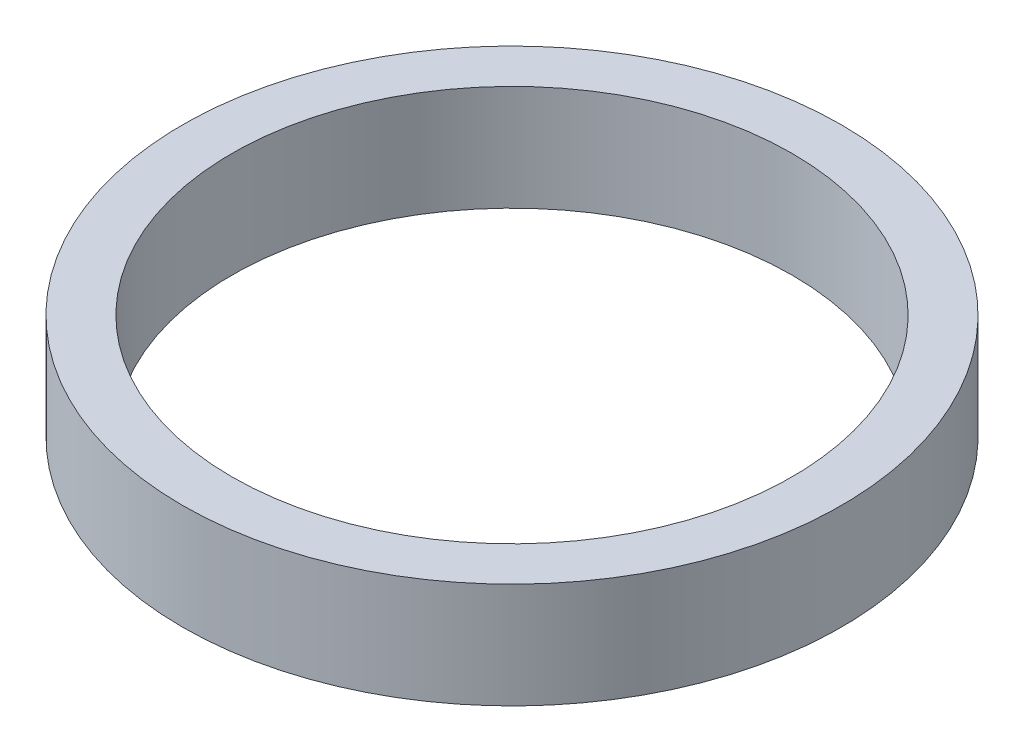
SolidWorks part; units mm, degrees
ref_plane "Front Plane" through (0, 0, 0) normal (0, 0, 1) x (1, 0, 0)
ref_plane "Top Plane" through (0, 0, 0) normal (0, 1, 0) x (1, 0, 0)
ref_plane "Right Plane" through (0, 0, 0) normal (1, 0, 0) x (0, 0, -1)
sketch "Sketch1" plane through (0, 0, 0) normal (0, 1, 0) x (1, 0, 0)
  circle A0 centre (0, 0) radius 50
  dimension "FLANGE_OD" = 100
extrude "Boss-Extrude1" add sketch "Sketch1" along normal blind 16
sketch "Sketch2" plane through (0, 0, 0) normal (0, 1, 0) x (1, 0, 0)
  circle A0 centre (0, 0) radius 42.5
  dimension "BORE_D" = 85
extrude "Cut-Extrude1" cut sketch "Sketch2" along normal through all
sketch "Sketch3" plane through (0, 16, 0) normal (0, 1, 0) x (1, 0, 0)
  circle A0 centre (0, 0) radius 23.3498 construction
  circle A1 centre (-23.3498, 0) radius 1.5
  dimension "BOLT_D" = 3
  dimension "BOLT_PCD" = 46.6996
extrude "Cut-Extrude2" cut sketch "Sketch3" against normal blind 13.4143 rebuild error yes
pattern_circular "CirPattern1" count 6 over 360 rebuild error yes
